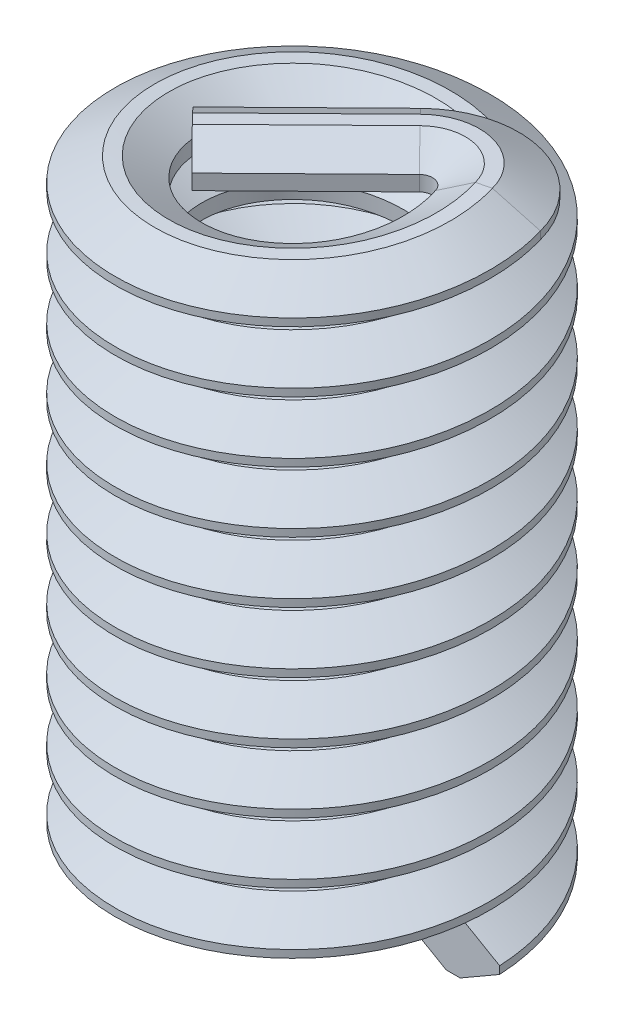
SolidWorks part; units mm, degrees
ref_plane "Front Plane" through (0, 0, 0) normal (0, 0, 1) x (1, 0, 0)
ref_plane "Top Plane" through (0, 0, 0) normal (0, 1, 0) x (1, 0, 0)
ref_plane "Right Plane" through (0, 0, 0) normal (1, 0, 0) x (0, 0, -1)
sketch "Sketch1" plane through (0, 0, 0) normal (0, 0, 1) x (-1, 0, 0)
  line L0 (0, 0) -> (0, 9.525) construction
  line L1 (-1.1511, 0) -> (-1.8385, 0.3969) construction
  line L2 (-1.8496, 0.3969) -> (-2.537, 0) construction
  line L3 (-2.537, 0) -> (-1.8496, -0.3969) construction
  line L4 (-1.8385, -0.3969) -> (-1.1511, 0) construction
  line L5 (-1.8385, -0.3969) -> (-1.8385, 0.3969) construction
  line L6 (-1.1511, 0) -> (0, 0) construction
  line L8 (-2.4511, -0.0496) -> (-1.9355, -0.3473)
  line L9 (-1.7526, -0.3473) -> (-1.323, -0.0992)
  line L10 (-1.237, -0.0496) -> (-1.237, 0.0496) construction
  line L11 (-1.323, 0.0992) -> (-1.7526, 0.3473)
  line L12 (-1.9355, 0.3473) -> (-2.4511, 0.0496)
  line L13 (-1.1511, 0) -> (-1.237, 0) construction
  line L14 (-1.237, 0) -> (-1.7526, 0) construction
  line L15 (-1.9355, 0) -> (-2.4511, 0) construction
  line L16 (-2.4511, 0) -> (-2.537, 0) construction
  line L17 (-1.9355, 0.3473) -> (-1.7526, 0.3473)
  line L18 (-1.7526, 0.3473) -> (-1.7526, -0.3473) construction
  line L19 (-1.7526, -0.3473) -> (-1.9355, -0.3473)
  line L20 (-1.9355, -0.3473) -> (-1.9355, 0.3473) construction
  line L21 (-1.9355, 0) -> (-1.8385, 0) construction
  line L22 (-1.8385, 0) -> (-1.7526, 0) construction
  line L23 (-2.4511, 0.3969) -> (-2.4511, -8.3661) construction
  line L24 (-1.323, -0.0992) -> (-1.323, 0.0992)
  line L25 (-1.323, 0) -> (-1.237, 0) construction
  line L26 (-2.4511, -0.0496) -> (-2.4511, 0.0496)
  line L28 (2.4511, 0.3969) -> (2.4511, -8.3661) construction
  line L29 (-1.8385, -0.3969) -> (-1.8496, -0.3969) construction
  line L31 (-1.8496, 0.3969) -> (-1.8385, 0.3969) construction
sketch "Sketch2" plane through (0, 0, 0) normal (0, 1, 0) x (1, 0, 0)
  circle A0 centre (0, 0) radius 1.7526
curve "Helix/Spiral1" pitch 0.7937 height 7.9692 turns 10.04 parameters "Height"=7.9692, "Pitch"=0.7937
sweep "Sweep1" add profiles "Sketch1" path "Helix/Spiral1"
sketch "Sketch3" plane through (0, 0, 0) normal (-0.2487, 0, -0.9686) x (-0.9686, 0, 0.2487)
  line L0 (-7.4107, 4.3549) -> (-1.1511, 7.9688) construction
  line L1 (-6.5587, 11.0909) -> (-1.1511, 7.9688) construction
  line L2 (-1.1511, 7.9688) -> (-1.1511, 8.1673) construction
  line L8 (-1.7526, 7.6216) -> (-1.323, 7.8696)
  line L9 (-1.323, 7.8696) -> (-1.323, 8.0681)
  line L10 (-1.323, 8.0681) -> (-1.7526, 8.3161)
  line L12 (-1.9355, 8.3161) -> (-2.4511, 8.0185)
  line L13 (-2.4511, 8.0185) -> (-2.4511, 7.9192)
  line L14 (-2.4511, 7.9192) -> (-1.9355, 7.6216)
  line L16 (-1.7526, 7.6216) -> (-1.323, 7.8696)
  line L17 (-1.323, 7.8696) -> (-1.323, 8.0681)
  line L18 (-1.323, 8.0681) -> (-1.7526, 8.3161)
  line L20 (-1.9355, 8.3161) -> (-2.4511, 8.0185)
  line L21 (-2.4511, 8.0185) -> (-2.4511, 7.9192)
  line L22 (-2.4511, 7.9192) -> (-1.9355, 7.6216)
  line L23 (-1.7526, 8.3161) -> (-1.9355, 8.3161)
  line L24 (-1.7526, 8.3161) -> (-1.9355, 8.3161)
  line L25 (-1.9355, 7.6216) -> (-1.7526, 7.6216)
  line L26 (-1.9355, 7.6216) -> (-1.7526, 7.6216)
  dimension "D1" = 0
revolve "Revolve1" add sketch "Sketch3" angle 120 about L2
sketch "Sketch4" plane through (0.7122, 0, -0.6975) normal (-0.7145, 0, 0.6997) x (0.6997, 0, 0.7145)
  line L8 (-0.2089, 7.6216) -> (-0.0259, 7.6216)
  line L9 (-0.0259, 7.6216) -> (0.4037, 7.8696)
  line L10 (0.4037, 7.8696) -> (0.4037, 8.0681)
  line L11 (0.4037, 8.0681) -> (-0.0259, 8.3161)
  line L12 (-0.2089, 7.6216) -> (-0.0259, 7.6216)
  line L13 (-0.2089, 8.3161) -> (-0.7244, 8.0185)
  line L14 (-0.7244, 8.0185) -> (-0.7244, 7.9192)
  line L15 (-0.7244, 7.9192) -> (-0.2089, 7.6216)
  line L17 (-0.0259, 7.6216) -> (0.4037, 7.8696)
  line L18 (0.4037, 7.8696) -> (0.4037, 8.0681)
  line L19 (0.4037, 8.0681) -> (-0.0259, 8.3161)
  line L21 (-0.2089, 8.3161) -> (-0.7244, 8.0185)
  line L22 (-0.7244, 8.0185) -> (-0.7244, 7.9192)
  line L23 (-0.7244, 7.9192) -> (-0.2089, 7.6216)
  spline S4 degree 1 poles (1999.9718, 8.3198) (-2000.2019, 8.3125) knots -10932.279875 -10932.279875 10933.254144 10933.254144 only from (-0.0259, 8.3161) to (-0.2089, 8.3161)
  spline S5 degree 1 poles (-0.0259, 8.3161) (-0.2089, 8.3161) knots 0 0 1 1
  dimension "D1" = 0
extrude "Extrude1" add sketch "Sketch4" along normal blind 2.1031
sketch "Sketch5" plane through (0, 0, 0) normal (0, 1, 0) x (1, 0, 0)
  circle A0 centre (0, 0) radius 3.1368
equation "\"D3@Sketch1\" = \"Pitch@Helix/Spiral1\""
equation "\"D4@Sketch1\" = \"D3@Sketch1\"  * 1 / 8"
equation "\"D1@Extrude1\" = \"Thread Size@Sketch1\" * 0.6"
equation "\"Height@Helix/Spiral1\" = \"Installed Length@Sketch1\" - \"Pitch@Helix/Spiral1\""
